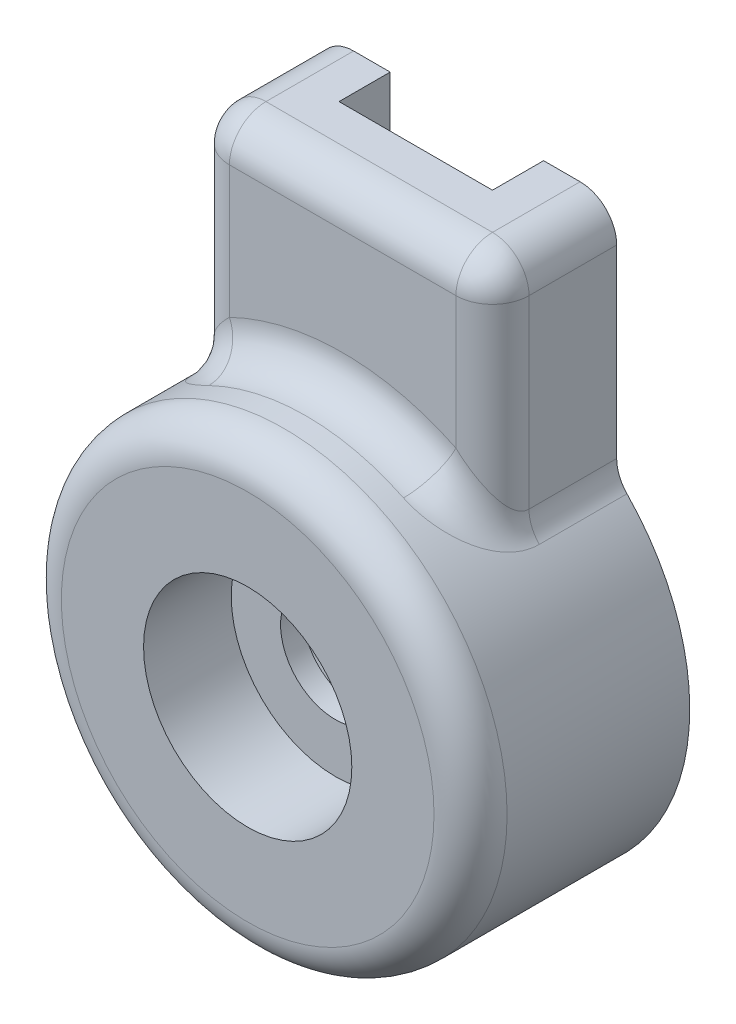
SolidWorks part; units mm, degrees
ref_plane "Front Plane" through (0, 0, 0) normal (0, 0, 1) x (1, 0, 0)
ref_plane "Top Plane" through (0, 0, 0) normal (0, 1, 0) x (1, 0, 0)
ref_plane "Right Plane" through (0, 0, 0) normal (1, 0, 0) x (0, 0, -1)
sketch "Sketch1" plane through (0, 0, 0) normal (0, 0, 1) x (1, 0, 0)
  line L0 (36.798, 101.1427) -> (103.7813, 99.6461) construction
  line L1 (0, 0) -> (0, 15) construction
  line L2 (0, 15) -> (-2.1, 15) construction
  line L3 (-2.1, 26.4786) -> (-2.1, 3.5214) construction
  line L4 (2.1, 26.4786) -> (2.1, 3.5214) construction
  line L5 (-2.1, 11) -> (-2.1, 3.5214)
  line L6 (2.1, 3.5214) -> (2.1, 11)
  line L7 (-4.1, 11) -> (-4.1, 4.5166)
  line L8 (4.1, 4.5166) -> (4.1, 11)
  line L9 (-2.1, 11) -> (-4.1, 11)
  line L10 (2.1, 11) -> (4.1, 11)
  circle A0 centre (0, 0) radius 4.1 construction
  circle A1 centre (0, 0) radius 2 construction
  arc A2 (2.1, 3.5214) -> (-2.1, 3.5214) centre (0, 0) cw construction
  circle A3 centre (0, 30) radius 2 construction
  arc A4 (2.1, 26.4786) -> (-2.1, 26.4786) centre (0, 30) ccw construction
  arc A5 (2.1, 3.5214) -> (-2.1, 3.5214) centre (0, 0) cw
  arc A6 (4.1, 4.5166) -> (-4.1, 4.5166) centre (0, 0) cw
  point P17 (2.1, 15)
  dimension "D2" = 4
  dimension "D3" = 2.1
  dimension "D6" = 2
  dimension "D1" = 67
  dimension "D4" = 2.1
  dimension "D5" = 15
  dimension "D7" = 4
extrude "Boss-Extrude1" add sketch "Sketch1" along normal blind 1.4 contours L5 A5 L6 L10 L8 A6 L7 L9
sketch "Sketch2" plane through (0, 0, 1.4) normal (0, 0, 1) x (1, 0, 0)
  line L0 (-2.1, 11) -> (-4.1, 11) construction
  line L1 (-4.1, 4.5166) -> (4.1, 4.5166)
  line L2 (-4.1, 4.5166) -> (-4.1, 11)
  line L3 (-4.1, 11) -> (4.1, 11)
  line L4 (4.1, 4.5166) -> (4.1, 11)
  line L5 (-4.1, 4.5166) -> (4.1, 11) construction
  line L6 (-4.1, 11) -> (4.1, 4.5166) construction
  line L7 (-4.1, 11) -> (-4.1, 4.5166) construction
  line L8 (4.1, 4.5166) -> (4.1, 11) construction
  point P0 (0, 7.7583)
extrude "Boss-Extrude2" add sketch "Sketch2" along normal blind 2
ref_axis "Axis1" through (0, 0, 6.0327) along (0, 0, -1)
sketch "Sketch3" plane through (0, 0, 0) normal (1, 0, 0) x (0, 0, -1)
  line L0 (-1.4, -6.1) -> (-6, -6.1)
  line L1 (-6, -6.1) -> (-6, -2.85)
  line L2 (-6, -2.85) -> (-3.6, -2.85)
  line L3 (-3.6, -2.85) -> (-3.6, 0)
  line L4 (1.87, 0) -> (-1.87, 0) construction
  line L5 (-3.6, 0) -> (-3, 0)
  line L6 (-3, 0) -> (-3, -4.1)
  line L7 (-3, -4.1) -> (-1.4, -4.1)
  line L8 (-1.4, 4.5166) -> (-1.4, -6.1) construction
  line L9 (-1.4, -4.1) -> (-1.4, -6.1)
  line L10 (-6.0327, 0) -> (1.4381, 0) construction
  line L11 (0, -6.1) -> (0, 4.5166) construction
  dimension "D1" = 3
  dimension "D2" = 0.6
  dimension "D3" = 2.4
  dimension "D4" = 2
  dimension "D5" = 2.85
revolve "Revolve1" add sketch "Sketch3" angle 360 about axis through (0, 0, 6.0327) along (0, 0, -1)
fillet "Fillet1" radius 1 9 edges at (6.1, 0, 6) (4.1, 11, 1.7) (4.1, 7.7583, 3.4) (-4.1, 11, 1.7) (0, 11, 3.4) (-4.1, 7.7583, 3.4) (-4.1, 4.5166, 1.7) (4.1, 4.5166, 1.7) (0, 6.1, 3.4)
sketch "Sketch4" plane through (0, 0, 3.6) normal (0, 0, 1) x (1, 0, 0)
  circle A0 centre (0, 0) radius 1.5
  dimension "D1" = 3
extrude "Cut-Extrude1" cut sketch "Sketch4" against normal blind 10
fillet "Fillet2" radius 10 2 edges at (-2.1, 3.5214, 0.7) (2.1, 3.5214, 0.7)
